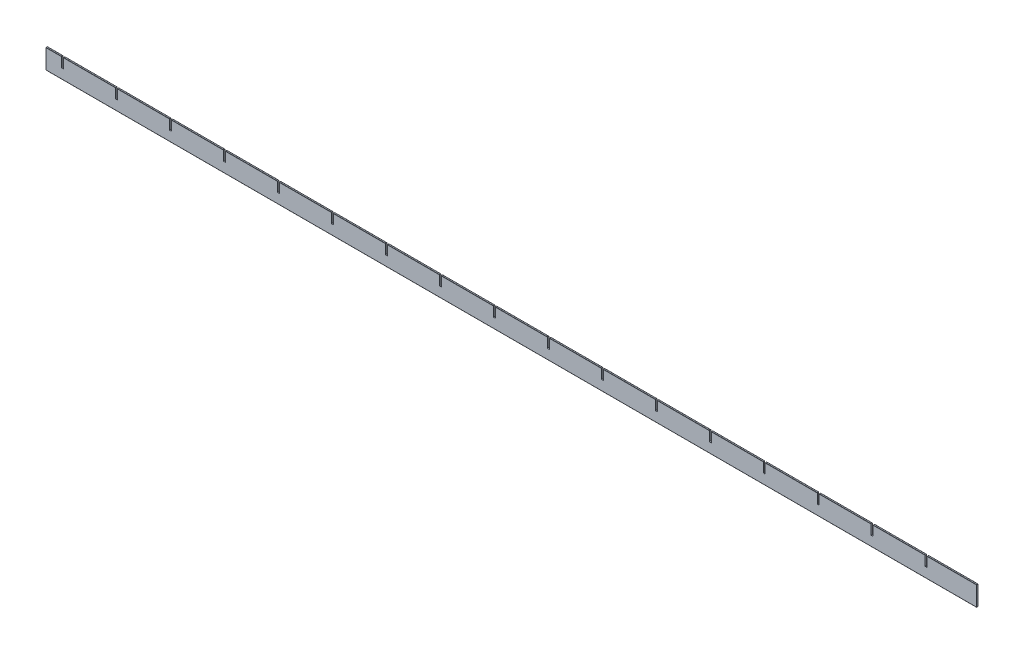
SolidWorks part; units mm, degrees
material "Alloy Steel"
ref_plane "Front Plane" through (0, 0, 0) normal (0, 0, 1) x (1, 0, 0)
ref_plane "Top Plane" through (0, 0, 0) normal (0, 1, 0) x (1, 0, 0)
ref_plane "Right Plane" through (0, 0, 0) normal (1, 0, 0) x (0, 0, -1)
sketch "Sketch1" plane through (0, 0, 0) normal (0, 0, 1) x (1, 0, 0)
  line L1 (948, -20) -> (-948, -20)
  line L2 (948, -20) -> (948, 20)
  line L3 (948, 20) -> (-948, 20)
  line L4 (-948, -20) -> (-948, 20)
  line L5 (948, -20) -> (-948, 20) construction
  line L6 (948, 20) -> (-948, -20) construction
  point P0 (0, 0)
  dimension "D1" = 1896
  dimension "D2" = 40
extrude "Boss-Extrude1" add sketch "Sketch1" along normal blind 1.5 and the other way blind 1.5
fillet "Fillet1" radius 0.35 4 edges at (0, -20, -1.5) (0, -20, 1.5) (0, 20, -1.5) (0, 20, 1.5)
sketch "Sketch2" plane through (0, 0, 1.5) normal (0, 0, 1) x (1, 0, 0)
  line L0 (-948, 20) -> (-914.51, 20) construction
  line L1 (-948, 20) -> (948, 20) construction
  line L2 (-802.51, 20) -> (-802.51, 0)
  line L3 (-916.51, 20) -> (-912.51, 20)
  line L4 (-916.51, 20) -> (-916.51, 0)
  line L5 (-916.51, 0) -> (-912.51, 0)
  line L6 (-912.51, 20) -> (-912.51, 0)
  line L7 (-806.51, 0) -> (-802.51, 0)
  line L8 (-806.51, 20) -> (-806.51, 0)
  line L9 (-806.51, 20) -> (-802.51, 20)
  line L10 (-692.51, 20) -> (-692.51, 0)
  line L11 (-696.51, 0) -> (-692.51, 0)
  line L12 (-696.51, 20) -> (-696.51, 0)
  line L13 (-696.51, 20) -> (-692.51, 20)
  line L14 (-582.51, 20) -> (-582.51, 0)
  line L15 (-586.51, 0) -> (-582.51, 0)
  line L16 (-586.51, 20) -> (-586.51, 0)
  line L17 (-586.51, 20) -> (-582.51, 20)
  line L18 (-472.51, 20) -> (-472.51, 0)
  line L19 (-476.51, 0) -> (-472.51, 0)
  line L20 (-476.51, 20) -> (-476.51, 0)
  line L21 (-476.51, 20) -> (-472.51, 20)
  line L22 (-362.51, 20) -> (-362.51, 0)
  line L23 (-366.51, 0) -> (-362.51, 0)
  line L24 (-366.51, 20) -> (-366.51, 0)
  line L25 (-366.51, 20) -> (-362.51, 20)
  line L26 (-252.51, 20) -> (-252.51, 0)
  line L27 (-256.51, 0) -> (-252.51, 0)
  line L28 (-256.51, 20) -> (-256.51, 0)
  line L29 (-256.51, 20) -> (-252.51, 20)
  line L30 (-142.51, 20) -> (-142.51, 0)
  line L31 (-146.51, 0) -> (-142.51, 0)
  line L32 (-146.51, 20) -> (-146.51, 0)
  line L33 (-146.51, 20) -> (-142.51, 20)
  line L34 (-32.51, 20) -> (-32.51, 0)
  line L35 (-36.51, 0) -> (-32.51, 0)
  line L36 (-36.51, 20) -> (-36.51, 0)
  line L37 (-36.51, 20) -> (-32.51, 20)
  line L38 (77.49, 20) -> (77.49, 0)
  line L39 (73.49, 0) -> (77.49, 0)
  line L40 (73.49, 20) -> (73.49, 0)
  line L41 (73.49, 20) -> (77.49, 20)
  line L42 (187.49, 20) -> (187.49, 0)
  line L43 (183.49, 0) -> (187.49, 0)
  line L44 (183.49, 20) -> (183.49, 0)
  line L45 (183.49, 20) -> (187.49, 20)
  line L46 (297.49, 20) -> (297.49, 0)
  line L47 (293.49, 0) -> (297.49, 0)
  line L48 (293.49, 20) -> (293.49, 0)
  line L49 (293.49, 20) -> (297.49, 20)
  line L50 (407.49, 20) -> (407.49, 0)
  line L51 (403.49, 0) -> (407.49, 0)
  line L52 (403.49, 20) -> (403.49, 0)
  line L53 (403.49, 20) -> (407.49, 20)
  line L54 (517.49, 20) -> (517.49, 0)
  line L55 (513.49, 0) -> (517.49, 0)
  line L56 (513.49, 20) -> (513.49, 0)
  line L57 (513.49, 20) -> (517.49, 20)
  line L58 (627.49, 20) -> (627.49, 0)
  line L59 (623.49, 0) -> (627.49, 0)
  line L60 (623.49, 20) -> (623.49, 0)
  line L61 (623.49, 20) -> (627.49, 20)
  line L62 (737.49, 20) -> (737.49, 0)
  line L63 (733.49, 0) -> (737.49, 0)
  line L64 (733.49, 20) -> (733.49, 0)
  line L65 (733.49, 20) -> (737.49, 20)
  line L66 (847.49, 20) -> (847.49, 0)
  line L67 (843.49, 0) -> (847.49, 0)
  line L68 (843.49, 20) -> (843.49, 0)
  line L69 (843.49, 20) -> (847.49, 20)
  line L70 (-912.51, 20) -> (-802.51, 20) construction
  dimension "D1" = 33.49
  dimension "D2" = 20
  dimension "D3" = 4
  dimension "D4" = 2
  dimension "D6" = 110
  dimension "D5" = 17
extrude "Cut-Extrude1" cut sketch "Sketch2" against normal through all
